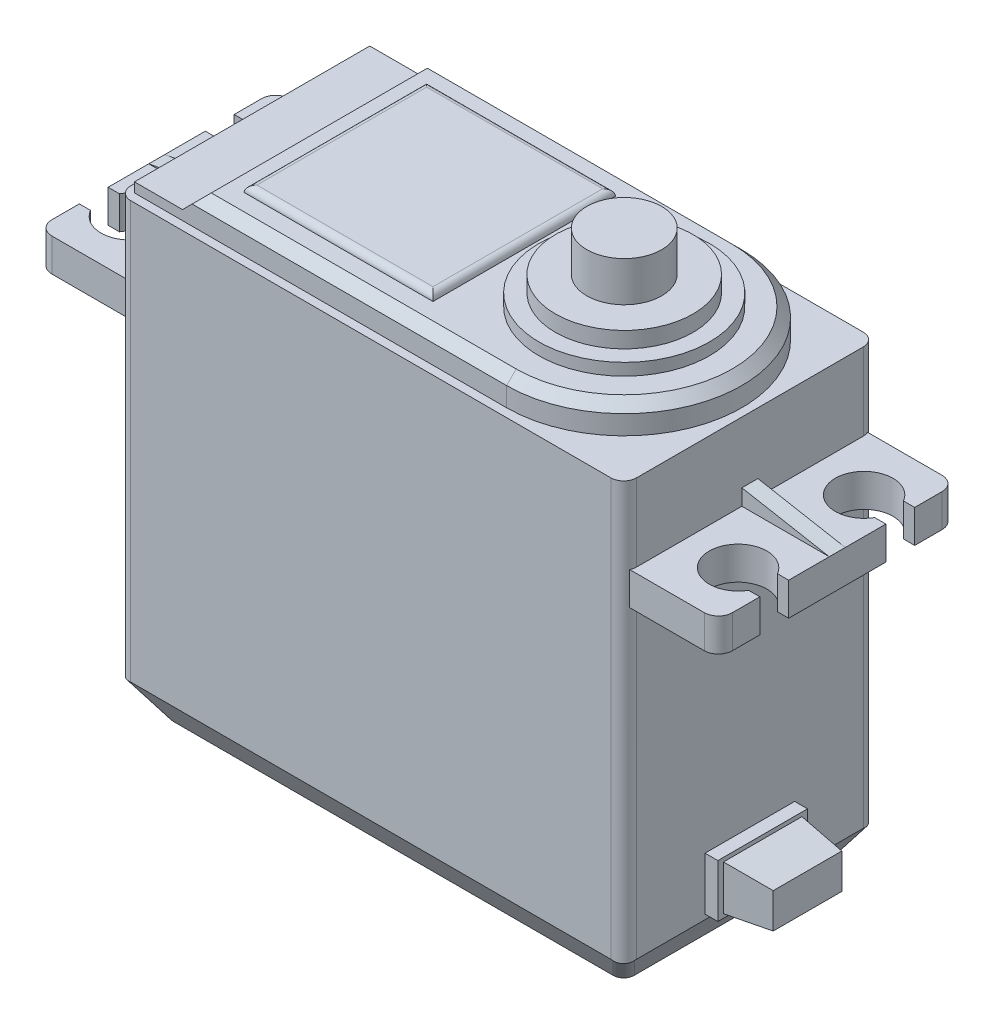
SolidWorks part; units mm, degrees
ref_plane "Front Plane" through (0, 0, 0) normal (0, 0, 1) x (1, 0, 0)
ref_plane "Top Plane" through (0, 0, 0) normal (0, 1, 0) x (1, 0, 0)
ref_plane "Right Plane" through (0, 0, 0) normal (1, 0, 0) x (0, 0, -1)
sketch "Sketch1" plane through (0, 0, 0) normal (0, 1, 0) x (1, 0, 0)
  line L1 (0, 0) -> (40.132, 0)
  line L2 (0, 0) -> (0, 20.0279)
  line L3 (0, 20.0279) -> (40.132, 20.0279)
  line L4 (40.132, 0) -> (40.132, 20.0279)
  dimension "D1" = 40.132
  dimension "D2" = 20.0279
extrude "Boss-Extrude1" add sketch "Sketch1" along normal blind 35.8775
chamfer "Chamfer1" distance 1.778 distance2 2.794 4 edges at (20.066, 0, 0) (40.132, 0, -10.0139) (20.066, 0, -20.0279) (0, 0, -10.0139) first distance on face at (20.066, 0, -10.0139)
sketch "Sketch2" plane through (40.132, 0, 0) normal (1, 0, 0) x (0, 0, -1)
  line L0 (10.0139, 2.794) -> (10.0139, 42.6327) construction
  line L1 (6.4579, 3.175) -> (13.5699, 3.175)
  line L2 (6.4579, 3.175) -> (6.4579, 7.366)
  line L3 (6.4579, 7.366) -> (13.5699, 7.366)
  line L4 (13.5699, 3.175) -> (13.5699, 7.366)
  line L5 (0, 2.794) -> (20.0279, 2.794) construction
  line L6 (18.2499, 0) -> (1.778, 0) construction
  point P8 (10.0139, 7.366)
  dimension "D1" = 7.112
  dimension "D2" = 4.191
  dimension "D3" = 7.366
extrude "Boss-Extrude2" add sketch "Sketch2" along normal blind 1.016
sketch "Sketch3" plane through (41.148, 0, 0) normal (1, 0, 0) x (0, 0, -1)
  line L0 (13.5699, 7.366) -> (6.4579, 7.366) construction
  line L1 (6.9024, 3.4925) -> (13.1254, 3.4925)
  line L2 (6.9024, 3.4925) -> (6.9024, 7.0485)
  line L3 (6.9024, 7.0485) -> (13.1254, 7.0485)
  line L4 (13.1254, 3.4925) -> (13.1254, 7.0485)
  line L5 (6.9024, 3.4925) -> (13.1254, 7.0485) construction
  line L6 (6.9024, 7.0485) -> (13.1254, 3.4925) construction
  line L7 (6.4579, 7.366) -> (6.4579, 3.175) construction
  point P0 (10.0139, 5.2705)
  point P7 (10.0139, 7.366)
  point P10 (6.4579, 5.2705)
  dimension "D1" = 3.556
  dimension "D2" = 6.223
extrude "Boss-Extrude3" add sketch "Sketch3" along normal blind 3.556
chamfer "Chamfer2" distance 3.556 angle 6.25 4 edges at (44.704, 3.4925, -10.0139) (44.704, 5.2705, -6.9024) (44.704, 7.0485, -10.0139) (44.704, 5.2705, -13.1254) first distance on face at (42.926, 3.4925, -10.0139) first distance on face at (42.926, 5.2705, -6.9024) first distance on face at (42.926, 7.0485, -10.0139) first distance on face at (42.926, 5.2705, -13.1254)
sketch "Sketch4" plane through (40.132, 0, 0) normal (1, 0, 0) x (0, 0, -1)
  line L0 (18.2499, 0) -> (1.778, 0) construction
  line L1 (0.5778, 27.1272) -> (19.45, 27.1272)
  line L2 (0.5778, 27.1272) -> (0.5778, 29.7434)
  line L3 (0.5778, 29.7434) -> (19.45, 29.7434)
  line L4 (19.45, 27.1272) -> (19.45, 29.7434)
  line L5 (0.5778, 27.1272) -> (19.45, 29.7434) construction
  line L6 (0.5778, 29.7434) -> (19.45, 27.1272) construction
  line L7 (0, 35.8775) -> (20.0279, 35.8775) construction
  point P0 (10.0139, 28.4353)
  point P9 (10.0139, 35.8775)
  dimension "D1" = 27.1272
  dimension "D2" = 2.6162
  dimension "D3" = 18.8722
extrude "Boss-Extrude4" add sketch "Sketch4" along normal blind 6.9342
ref_plane "Plane1" through (0, 0, -10.0139) normal (0, 0, 1) x (1, 0, 0)
sketch "Sketch8" plane through (0, 0, -10.0139) normal (0, 0, 1) x (1, 0, 0)
  line L0 (40.132, 35.8775) -> (40.132, 2.794) construction
  line L1 (47.0662, 29.7434) -> (40.132, 29.7434) construction
  line L2 (40.132, 35.8775) -> (40.132, 2.794) construction
  line L3 (47.0662, 29.7434) -> (40.132, 29.7434)
  line L4 (40.132, 31.0134) -> (47.0662, 29.7434)
  line L6 (40.132, 29.7434) -> (40.132, 31.0134)
  dimension "D1" = 1.27
extrude "Boss-Extrude5" add sketch "Sketch8" along normal blind 0.635 and the other way blind 0.635
sketch "Sketch9" plane through (0, 29.7434, 0) normal (0, 1, 0) x (1, 0, 0)
  line L0 (47.0662, 10.0139) -> (36.1767, 10.0139) construction
  line L1 (47.0662, 10.6489) -> (47.0662, 9.3789) construction
  line L2 (47.0662, 3.8709) -> (46.1757, 3.8709)
  line L3 (46.1757, 13.8709) -> (47.0662, 13.8709)
  line L4 (47.0662, 13.8709) -> (47.0662, 16.1569)
  line L5 (47.0662, 16.1569) -> (46.1757, 16.1569)
  line L6 (47.0662, 6.1569) -> (47.0662, 3.8709)
  line L7 (47.0662, 19.4501) -> (47.0662, 10.6489) construction
  line L8 (40.132, 19.4501) -> (40.132, 10.6489) construction
  line L9 (46.1757, 6.1569) -> (47.0662, 6.1569)
  arc A0 (46.1757, 3.8709) -> (46.1757, 6.1569) centre (44.196, 5.0139) cw
  arc A2 (46.1757, 16.1569) -> (46.1757, 13.8709) centre (44.196, 15.0139) ccw
  dimension "D1" = 2.286
  dimension "D2" = 4.064
  dimension "D3" = 5
  dimension "D4" = 2.286
extrude "Cut-Extrude1" cut sketch "Sketch9" against normal up to next
fillet "Fillet2" radius 1.1176 2 edges at (47.0662, 28.4353, -0.5779) (47.0662, 28.4353, -19.4501)
ref_plane "Plane2" through (20.066, 0, 0) normal (1, 0, 0) x (0, 0, -1)
mirror "Mirror3" about plane through (20.066, 0, 0) normal (1, 0, 0) of "Boss-Extrude4", "Boss-Extrude5", "Fillet2", "Cut-Extrude1"
sketch "Sketch10" plane through (0, 35.8775, 0) normal (0, 1, 0) x (1, 0, 0)
  line L0 (30.1625, 0.6795) -> (0.635, 0.6795)
  line L1 (0.635, 0.6795) -> (0.635, 19.3484)
  line L2 (0.635, 19.3484) -> (30.1625, 19.3484)
  line L6 (-18.1959, 10.0139) -> (18.1959, 10.0139) construction
  line L7 (39.497, 10.0139) -> (0.635, 10.0139) construction
  line L9 (20.066, -11.0153) -> (20.066, 11.0153) construction
  arc A0 (30.1625, 0.6795) -> (30.1625, 19.3484) centre (30.1625, 10.0139) ccw
  point P5 (0.635, 10.0139)
  point P8 (39.497, 10.0139)
  point P11 (20.066, 10.0139)
  dimension "D1" = 18.669
  dimension "D2" = 38.862
extrude "Boss-Extrude6" add sketch "Sketch10" along normal blind 2.286
chamfer "Chamfer3" distance 0.762 angle 45 4 edges at (15.3988, 38.1635, -0.6795) (0.635, 38.1635, -10.0139) (15.3988, 38.1635, -19.3484) (39.497, 38.1635, -10.0139)
sketch "Sketch11" plane through (0, 0, -19.3484) normal (0, 0, -1) x (-1, 0, 0)
  line L0 (-30.1625, 38.1635) -> (-1.397, 38.1635) construction
  line L1 (-30.1625, 38.1635) -> (-1.397, 38.1635) construction
  line L2 (-0.635, 36.6395) -> (-4.445, 36.6395)
  line L3 (-0.635, 37.4015) -> (-0.635, 35.8775) construction
  line L4 (-4.445, 36.6395) -> (-5.969, 38.1635)
  line L5 (-5.969, 38.1635) -> (-0.635, 38.1635)
  line L6 (-0.635, 38.1635) -> (-0.635, 36.6395)
  dimension "D1" = 3.81
  dimension "D2" = 45
extrude "Cut-Extrude2" cut sketch "Sketch11" against normal through all
fillet "Fillet3" radius 1.016 8 edges at (0, 19.3358, 0) (0.889, 1.397, -0.889) (0.889, 1.397, -19.1389) (0, 19.3358, -20.0279) (39.243, 1.397, -19.1389) (39.243, 1.397, -0.889) (40.132, 19.3358, 0) (40.132, 19.3358, -20.0279)
sketch "Sketch12" plane through (0, 38.1635, 0) normal (0, 1, 0) x (1, 0, 0)
  arc A0 (30.1625, 1.4415) -> (30.1625, 18.5864) centre (30.1625, 10.0139) ccw construction
  arc A1 (30.1625, 1.4415) -> (30.1625, 18.5864) centre (30.1625, 10.0139) ccw construction
  circle A2 centre (30.1625, 10.0139) radius 6.7691
  dimension "D1" = 13.5382
extrude "Boss-Extrude7" add sketch "Sketch12" along normal blind 0.9525
sketch "Sketch13" plane through (0, 39.116, 0) normal (0, 1, 0) x (1, 0, 0)
  circle A0 centre (30.1625, 10.0139) radius 5.461
  dimension "D1" = 10.922
extrude "Boss-Extrude8" add sketch "Sketch13" along normal blind 1.27
sketch "Sketch15" plane through (0, 40.386, 0) normal (0, 1, 0) x (1, 0, 0)
  circle A0 centre (30.1625, 10.0139) radius 2.9718
  dimension "D1" = 5.9436
extrude "Boss-Extrude9" add sketch "Sketch15" along normal blind 3.175
sketch "Sketch16" plane through (0, 38.1635, 0) normal (0, 1, 0) x (1, 0, 0)
  line L0 (5.969, 1.4415) -> (5.969, 18.5864) construction
  line L1 (22.225, 17.2529) -> (7.239, 17.2529)
  line L2 (22.225, 17.2529) -> (22.225, 2.7749)
  line L3 (22.225, 2.7749) -> (7.239, 2.7749)
  line L4 (7.239, 17.2529) -> (7.239, 2.7749)
  line L5 (22.225, 17.2529) -> (7.239, 2.7749) construction
  line L6 (22.225, 2.7749) -> (7.239, 17.2529) construction
  point P0 (14.732, 10.0139)
  point P7 (5.969, 10.0139)
  dimension "D1" = 14.986
  dimension "D2" = 14.478
  dimension "D3" = 1.27
extrude "Boss-Extrude10" add sketch "Sketch16" along normal blind 0.508
fillet "Fillet4" radius 0.508 4 edges at (14.732, 38.6715, -17.2529) (22.225, 38.6715, -10.0139) (14.732, 38.6715, -2.7749) (7.239, 38.6715, -10.0139)
